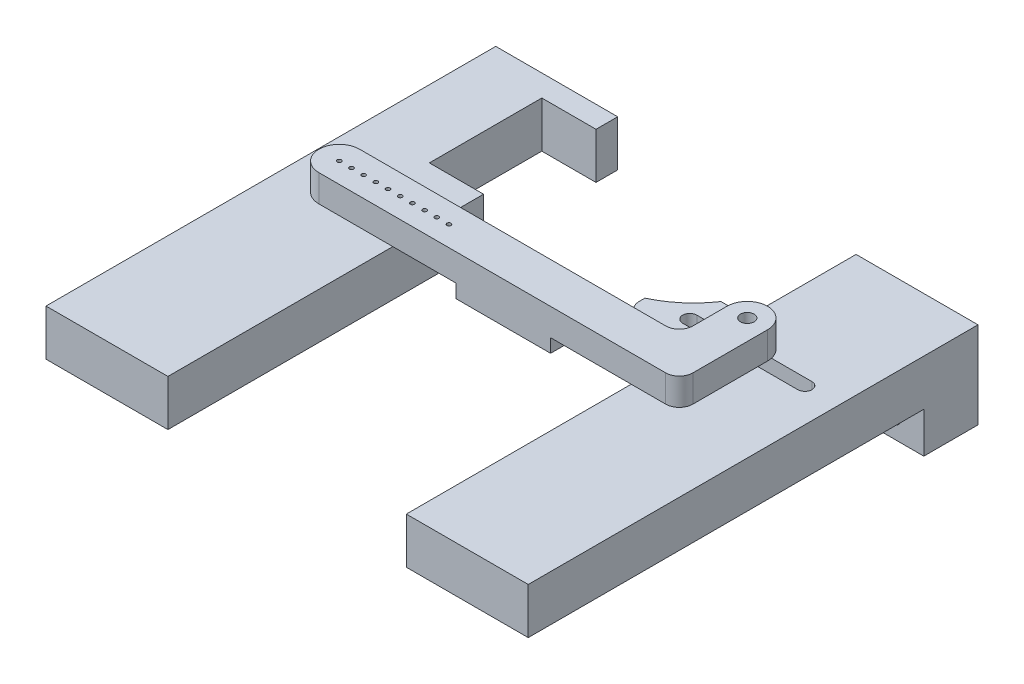
SolidWorks part; units mm, degrees
ref_plane "Front" through (0, 0, 0) normal (0, 0, 1) x (1, 0, 0)
ref_plane "Top" through (0, 0, 0) normal (0, 1, 0) x (1, 0, 0)
ref_plane "Right" through (0, 0, 0) normal (1, 0, 0) x (0, 0, -1)
sketch "Sketch1" plane through (0, 0, 0) normal (0, 1, 0) x (1, 0, 0)
  line L0 (0, 0) -> (0.465, -112) construction
  line L1 (88.995, 54) -> (38.065, 54)
  line L2 (88.995, 54) -> (88.995, -112)
  line L4 (38.065, 54) -> (38.065, 35)
  line L5 (3.065, 0) -> (-3.065, 0)
  line L9 (88.995, -112) -> (-88.065, -112)
  line L10 (-38.065, 35) -> (-38.065, 54)
  line L11 (-38.065, 54) -> (-88.065, 54)
  line L12 (-88.065, -112) -> (-88.065, 54)
  arc A0 (-3.065, 0) -> (-38.065, 35) centre (-3.065, 35) cw
  arc A1 (3.065, 0) -> (38.065, 35) centre (3.065, 35) ccw
  point P11 (0, 0)
  point P14 (-38.065, 0)
  point P18 (38.065, 0)
  dimension "D6" = 35
  dimension "D1" = 50.93
  dimension "D2" = 54
  dimension "D3" = 76.13
  dimension "D4" = 50
  dimension "D5" = 166
sketch "Sketch2" plane through (0, 0, 0) normal (0, 1, 0) x (1, 0, 0)
  line L0 (88.995, -112) -> (-88.065, -112) construction
  line L1 (88.995, 54) -> (43.995, 54)
  line L2 (88.995, 54) -> (88.995, -112)
  line L3 (88.995, -112) -> (43.995, -112)
  line L4 (43.995, 54) -> (43.995, -112)
  point P7 (88.995, 54)
  dimension "D1" = 45
extrude "Boss-Extrude1" add sketch "Sketch2" along normal blind 17
mirror "Mirror4" about plane through (0, 0, 0) normal (1, 0, 0) of bodies 103
sketch "Sketch6" plane through (0, 17, 0) normal (0, 1, 0) x (1, 0, 0)
  line L0 (43.995, 54) -> (43.995, -112) construction
  line L2 (43.995, 14) -> (43.995, -6)
  line L3 (43.995, -6) -> (18.995, -6)
  line L4 (88.995, 54) -> (38.065, 54) construction
  line L5 (43.995, 14) -> (34.1335, 14)
  line L6 (18.995, -6) -> (18.995, 1.0517)
  arc A1 (18.995, 1.0517) -> (34.1335, 14) centre (3.065, 35) ccw
  dimension "D3" = 75
  dimension "D1" = 40
  dimension "D2" = 20
  dimension "D4" = 25
extrude "Boss-Extrude3" add sketch "Sketch6" against normal up to surface (17 mm away) contours L2 L3 L6 A1 L5 up to face at (66.495, 0, 29)
sketch "Sketch3" plane through (0, 17, 0) normal (0, 1, 0) x (1, 0, 0)
  line L0 (33.995, 2.6) -> (76.495, 2.6) construction
  line L1 (33.995, 5.2) -> (76.495, 5.2)
  line L2 (33.995, 0) -> (76.495, 0)
  line L3 (3.065, 0) -> (-3.065, 0) construction
  line L6 (88.995, 54) -> (88.995, -112) construction
  line L8 (18.995, -6) -> (18.995, 1.0517) construction
  arc A1 (33.995, 5.2) -> (33.995, 0) centre (33.995, 2.6) ccw
  arc A2 (76.495, 0) -> (76.495, 5.2) centre (76.495, 2.6) ccw
  point P2 (55.245, 2.6)
  dimension "D1" = 2.6
  dimension "D2" = 15
  dimension "D3" = 12.5
extrude "Cut-Extrude1" cut sketch "Sketch3" against normal through all
sketch "Sketch4" plane through (0, 17, 0) normal (0, 1, 0) x (1, 0, 0)
  line L0 (57.745, -30) -> (-70.255, -30)
  line L1 (-70.255, -15) -> (42.745, -15)
  line L2 (3.065, 0) -> (-3.065, 0) construction
  line L3 (62.745, 2.6) -> (62.745, -25)
  line L4 (47.745, 2.6) -> (47.745, -10)
  line L7 (33.995, 2.6) -> (76.495, 2.6) construction
  circle A0 centre (55.245, 2.6) radius 2.5
  arc A1 (62.745, 2.6) -> (47.745, 2.6) centre (55.245, 2.6) ccw
  arc A2 (-70.255, -30) -> (-70.255, -15) centre (-70.255, -22.5) cw
  arc A10 (47.745, -10) -> (42.745, -15) centre (42.745, -10) cw
  arc A11 (62.745, -25) -> (57.745, -30) centre (57.745, -25) cw
  point P3 (38.5238, 2.6)
  point P18 (76.495, 2.6)
  point P20 (55.245, 2.6)
  dimension "D1" = 5
  dimension "D2" = 15
  dimension "D4" = 7.5
  dimension "D6" = 5
  dimension "D3" = 15
  dimension "D5" = 133
extrude "Boss-Extrude2" add sketch "Sketch4" along normal blind 10 from offset 1 separate body
sketch "Sketch5" plane through (0, 28, 0) normal (0, 1, 0) x (1, 0, 0)
  circle A0 centre (-70.255, -22.5) radius 0.75
  dimension "D1" = 1.5
extrude "Cut-Extrude2" cut sketch "Sketch5" against normal up to next (10 mm away)
pattern_linear "LPattern1" count 10 spacing 4.5 along (1, 0, 0) of "Cut-Extrude2"
sketch "Sketch7" plane through (0, 18, 0) normal (0, -1, 0) x (1, 0, 0)
  line L0 (-70.255, 30) -> (57.745, 30) construction
  line L1 (-19.755, 30) -> (15.245, 30)
  line L2 (-19.755, 30) -> (-19.755, 15)
  line L3 (-19.755, 15) -> (15.245, 15)
  line L4 (15.245, 30) -> (15.245, 15)
  line L5 (42.745, 15) -> (-70.255, 15) construction
  circle A0 centre (-29.755, 22.5) radius 0.75 construction
  dimension "D1" = 35
  dimension "D2" = 10
extrude "Boss-Extrude4" add sketch "Sketch7" along normal blind 5
fillet "Fillet1" radius 5 1 edges at (18.995, 8.5, 6)
sketch "Sketch8" plane through (0, 17, 0) normal (0, 1, 0) x (1, 0, 0)
  line L0 (-43.995, 54) -> (-43.995, -112) construction
  line L1 (-43.995, 46) -> (-63.995, 46)
  line L2 (-43.995, 46) -> (-43.995, 4.5)
  line L3 (-43.995, 4.5) -> (-63.995, 4.5)
  line L4 (-63.995, 46) -> (-63.995, 4.5)
  line L5 (-38.065, 54) -> (-88.065, 54) construction
  dimension "D1" = 20
  dimension "D2" = 41.5
  dimension "D3" = 8
extrude "Cut-Extrude3" cut sketch "Sketch8" against normal up to next (17 mm away)
sketch "Sketch9" plane through (0, 0, 0) normal (0, -1, 0) x (1, 0, 0)
  line L0 (88.995, -54) -> (88.995, 112) construction
  line L1 (43.995, -54) -> (88.995, -54)
  line L2 (43.995, -54) -> (43.995, -34)
  line L3 (43.995, -34) -> (88.995, -34)
  line L4 (88.995, -54) -> (88.995, -34)
  dimension "D1" = 20
extrude "Boss-Extrude5" add sketch "Sketch9" along normal blind 15
sketch "Sketch10" plane through (0, 0, -34) normal (0, 0, 1) x (1, 0, 0)
  line L0 (43.995, 0) -> (43.995, -15) construction
  line L1 (43.995, -7.5) -> (88.995, -7.5) construction
  line L2 (88.995, -15) -> (88.995, 0) construction
  circle A0 centre (53.4279, -7.5) radius 2.75
  circle A1 centre (77.8278, -7.5) radius 2.75
  point P12 (77.8278, -7.5)
  point P13 (53.4279, -7.5)
  dimension "D1" = 5.5
extrude "Cut-Extrude4" cut sketch "Sketch10" against normal up to next (20 mm away)
